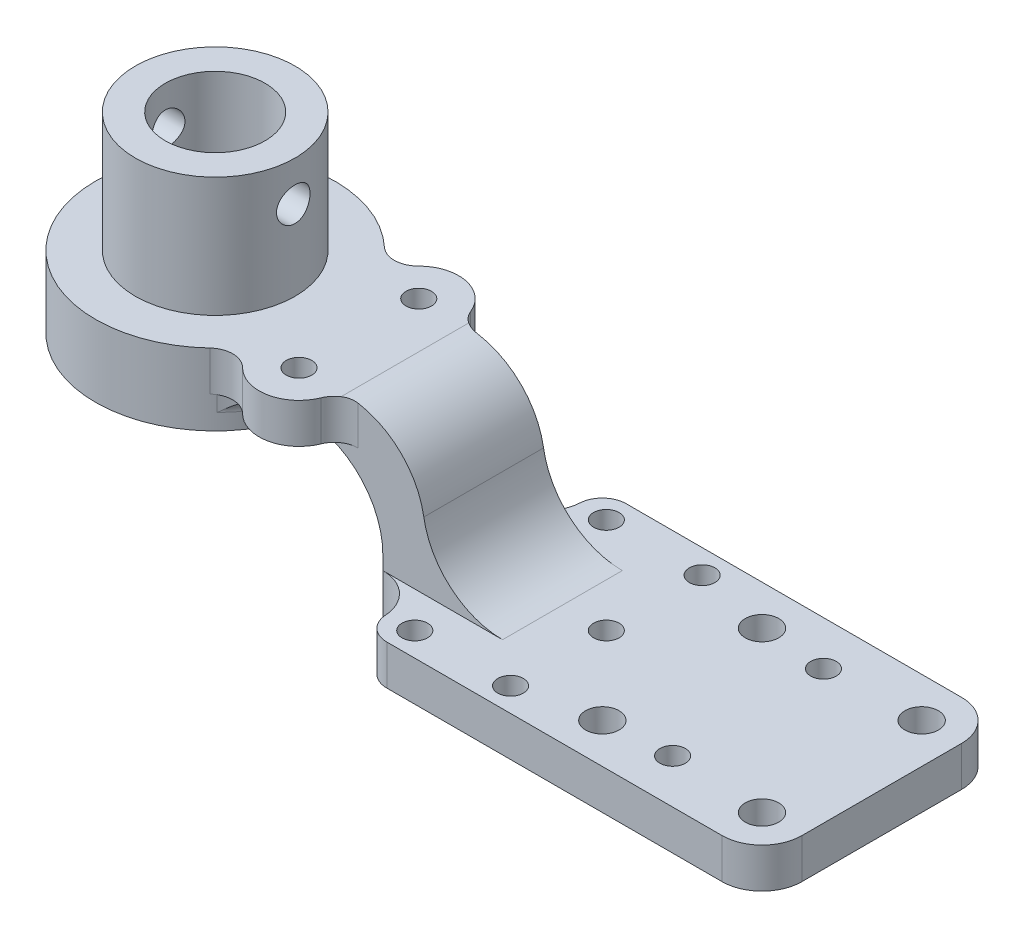
SolidWorks part; units mm, degrees
ref_plane "前视基准面" through (0, 0, 0) normal (0, 0, 1) x (1, 0, 0)
ref_plane "上视基准面" through (0, 0, 0) normal (0, 1, 0) x (1, 0, 0)
ref_plane "右视基准面" through (0, 0, 0) normal (1, 0, 0) x (0, 0, -1)
sketch "草图1" plane through (0, 0, 0) normal (0, 0, 1) x (1, 0, 0)
  line L0 (0, 0) -> (45, 0)
  line L1 (45, 0) -> (45, -16.75)
  line L2 (45, -16.75) -> (100, -16.75)
  line L3 (0, 5) -> (50, 5)
  line L4 (50, 5) -> (50, -11.75)
  line L5 (50, -11.75) -> (100, -11.75)
  line L6 (0, 5) -> (0, 0)
  line L7 (100, -11.75) -> (100, -16.75)
  dimension "D1" = 55
  dimension "D2" = 45
  dimension "D4" = 16.75
  dimension "D3" = 5
extrude "凸台-拉伸1" add sketch "草图1" along normal blind 30
sketch "草图2" plane through (0, 0, 0) normal (0, -1, 0) x (1, 0, 0)
  line L0 (0, 30) -> (0, 0) construction
  circle A0 centre (16.5, 15) radius 15
  circle A1 centre (16.5, 15) radius 12
  dimension "D1" = 30
  dimension "D3" = 24
  dimension "D2" = 16.5
extrude "凸台-拉伸2" add sketch "草图2" along normal blind 4
sketch "草图3" plane through (0, 0, 0) normal (0, -1, 0) x (1, 0, 0)
  line L0 (53.5, -984.2084) -> (53.5, 49015.7916) construction
  line L1 (65.5, -983.496) -> (65.5, 49016.504) construction
  line L2 (45, 30) -> (100, 30) construction
  circle A0 centre (16.5, 15) radius 10
  circle A1 centre (53.5, 27) radius 1.6
  circle A2 centre (65.5, 27) radius 1.6
  circle A3 centre (65.5, 3) radius 1.6
  circle A4 centre (53.5, 3) radius 1.6
  circle A5 centre (65.5, 15) radius 1.6
  dimension "D1" = 20
  dimension "D4" = 24
  dimension "D5" = 24
  dimension "D6" = 3.2
  dimension "D7" = 3.2
  dimension "D8" = 3.2
  dimension "D9" = 3.2
  dimension "D10" = 3
  dimension "D11" = 3
  dimension "D12" = 3.2
  dimension "D2" = 37
  dimension "D3" = 12
extrude "切除-拉伸1" cut sketch "草图3" against normal through all and the other way through all
sketch "草图4" plane through (0, 0, 0) normal (0, -1, 0) x (1, 0, 0)
  line L0 (-1.3425, 47.8966) -> (16.5, 30)
  line L1 (-17.0025, 21.6214) -> (-14.6903, -12.3262)
  line L2 (-1.3425, 47.8966) -> (-17.0025, 21.6214)
  line L5 (-14.6903, -12.3262) -> (16.5, 0)
  circle A0 centre (16.5, 15) radius 15 construction
  circle A1 centre (16.5, 15) radius 15 construction
  arc A2 (16.5, 30) -> (16.5, 0) centre (16.5, 15) ccw
extrude "切除-拉伸2" cut sketch "草图4" against normal blind 6 contours L5 | L5 region at (-3.6404, 0, 16.3538)
sketch "草图12" plane through (0, -11.75, 0) normal (0, 1, 0) x (1, 0, 0)
  line L0 (95, -1010.3905) -> (95, 48989.6095) construction
  line L1 (100, -30) -> (100, 0) construction
  line L2 (100, 0) -> (50, 0) construction
  line L3 (100, -30) -> (50, -30) construction
  line L4 (85, -1010.3905) -> (85, 48989.6095) construction
  circle A0 centre (95, -5) radius 2.1
  circle A1 centre (95, -25) radius 2.1
  circle A3 centre (75, -25) radius 2.1
  circle A4 centre (75, -5) radius 2.1
  dimension "D2" = 5
  dimension "D3" = 4.2
  dimension "D4" = 5
  dimension "D6" = 4.2
  dimension "D8" = 10
  dimension "D1" = 5
extrude "切除-拉伸7" cut sketch "草图12" against normal blind 10
sketch "草图13" plane through (0, -4, 0) normal (0, -1, 0) x (1, 0, 0)
  circle A0 centre (16.5, 15) radius 12
  dimension "D1" = 24
extrude "切除-拉伸8" cut sketch "草图13" against normal blind 6
fillet "圆角4" radius 5 2 edges at (100, -14.25, 0) (100, -14.25, 30)
sketch "草图20" plane through (0, 0, 0) normal (0, -1, 0) x (1, 0, 0)
  line L0 (-988.5, 15) -> (49011.5, 15) construction
  line L1 (50, 22.5) -> (50, 30)
  line L2 (45, 30) -> (95, 30) construction
  line L3 (50, 30) -> (45, 30)
  line L4 (45, 30) -> (16.5, 30)
  line L5 (29.4904, 22.5) -> (50, 22.5)
  line L6 (45, 30) -> (45, 0) construction
  line L7 (29.4904, 7.5) -> (50, 7.5)
  line L8 (50, 7.5) -> (50, 0)
  line L9 (50, 0) -> (45, 0)
  line L10 (45, 0) -> (16.5, 0)
  arc A0 (16.5, 0) -> (16.5, 30) centre (16.5, 15) ccw construction
  arc A1 (29.4904, 22.5) -> (16.5, 30) centre (16.5, 15) ccw
  arc A2 (29.4904, 7.5) -> (16.5, 0) centre (16.5, 15) cw
  dimension "D1" = 7.5
  dimension "D2" = 5
extrude "切除-拉伸12" cut sketch "草图20" against normal blind 10 and the other way blind 40
fillet "圆角5" radius 3 2 edges at (50, -14.25, 0) (50, -14.25, 30)
fillet "圆角6" radius 5 2 edges at (50, -14.25, 7.5) (50, -14.25, 22.5)
fillet "圆角7" radius 10 2 edges at (29.4904, 2.5, 7.5) (29.4904, 2.5, 22.5)
fillet "圆角8" radius 2 1 edges at (31.5, 0, 15)
fillet "圆角9" radius 10 1 edges at (50, -11.75, 15)
fillet "圆角10" radius 10 1 edges at (50, 5, 15)
fillet "圆角11" radius 10 1 edges at (45, 0, 15)
sketch "草图21" plane through (0, 5, 0) normal (0, 1, 0) x (1, 0, 0)
  circle A0 centre (16.5, -15) radius 10
  circle A1 centre (16.5, -15) radius 6.25
  dimension "D1" = 12.5
  dimension "D2" = 20
extrude "凸台-拉伸3" add sketch "草图21" along normal blind 15 and the other way up to surface (3 mm away) other way up to face at (16.5, 2, 3)
sketch "草图22" plane through (100, 0, 0) normal (1, 0, 0) x (0, 0, -1)
  line L0 (-15, -975) -> (-15, 49025) construction
  line L1 (-5, 20) -> (-25, 20) construction
  line L3 (0, 5) -> (-30, 5) construction
  circle A0 centre (-15, 15) radius 2.1
  point P5 (-15, 20)
  dimension "D2" = 4.2
  dimension "D1" = 10
extrude "切除-拉伸13" cut sketch "草图22" against normal through all
sketch "草图24" plane through (0, 5, 0) normal (0, 1, 0) x (1, 0, 0)
  line L0 (34.5, -1015.5982) -> (34.5, 48984.4018) construction
  line L1 (-983.5, -15) -> (49016.5, -15) construction
  circle A0 centre (16.5, -15) radius 10 construction
  circle A1 centre (34.5, -22.5) radius 1.6
  circle A2 centre (34.5, -22.5) radius 5
  circle A3 centre (16.5, -15) radius 6.25 construction
  circle A4 centre (34.5, -7.5) radius 5
  circle A5 centre (34.5, -7.5) radius 1.6
  dimension "D2" = 3.2
  dimension "D3" = 10
  dimension "D1" = 18
  dimension "D4" = 7.5
extrude "凸台-拉伸4" add sketch "草图24" against normal up to surface (5 mm away) up to face at (33.9552, 0, 15)
sketch "草图25" plane through (0, 5, 0) normal (0, 1, 0) x (1, 0, 0)
  circle A0 centre (34.5, -22.5) radius 1.6
  circle A2 centre (34.5, -7.5) radius 1.6
extrude "切除-拉伸14" cut sketch "草图25" against normal blind 10
sketch "草图26" plane through (0, -11.75, 0) normal (0, 1, 0) x (1, 0, 0)
  circle A0 centre (83.25, -5.5489) radius 1.6
  dimension "D1" = 3.2
extrude "切除-拉伸15" [suppressed] cut sketch "草图26" against normal blind 10
fillet "圆角13" radius 3 4 edges at (39.5, 2.5, 22.5) (39.5, 2.5, 7.5) (29.6412, 2.5, 6.3201) (29.6412, 2.5, 23.6799)
sketch "草图27" plane through (0, -11.75, 0) normal (0, 1, 0) x (1, 0, 0)
  line L0 (-983.5, -15) -> (49016.5, -15) construction
  circle A0 centre (83.25, -24.4511) radius 1.6
  circle A1 centre (83.25, -5.5489) radius 1.6
  circle A2 centre (83.25, -5.5489) radius 1.6
  dimension "D1" = 0
extrude "切除-拉伸16" cut sketch "草图27" against normal blind 10
